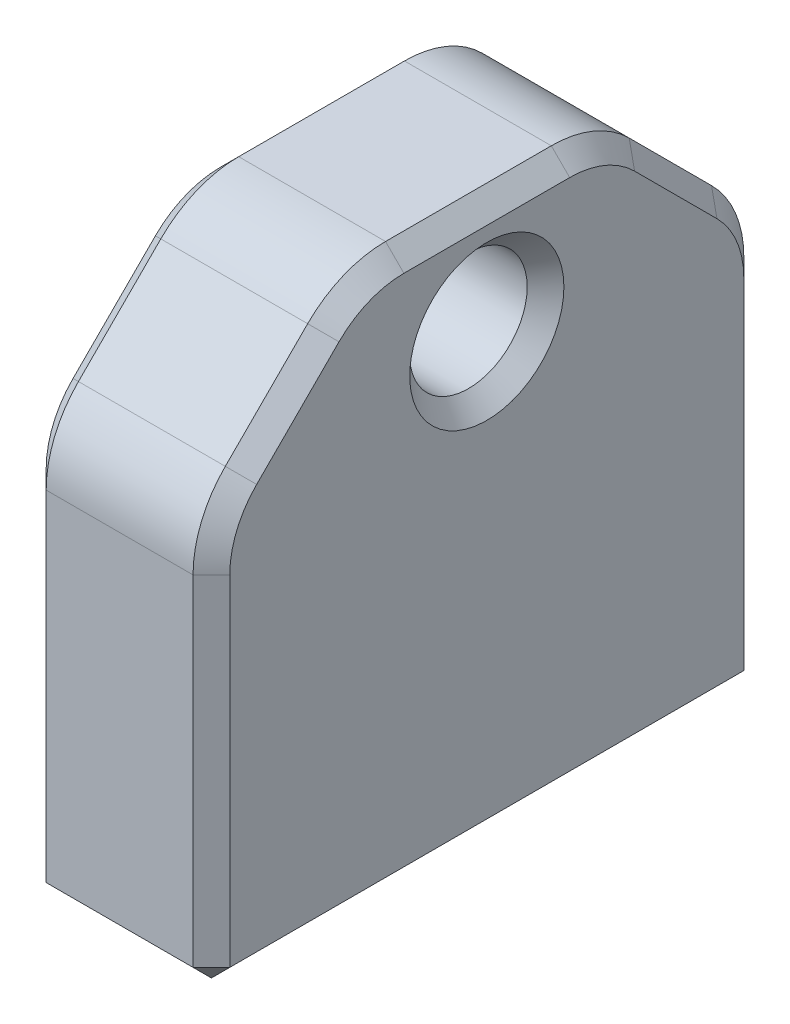
SolidWorks part; units mm, degrees
ref_plane "Front Plane" through (0, 0, 0) normal (0, 0, 1) x (1, 0, 0)
ref_plane "Top Plane" through (0, 0, 0) normal (0, 1, 0) x (1, 0, 0)
ref_plane "Right Plane" through (0, 0, 0) normal (1, 0, 0) x (0, 0, -1)
sketch "Sketch1" plane through (0, 0, 0) normal (0, 1, 0) x (1, 0, 0)
  line L0 (0, 6.35) -> (0, -6.35) construction
  line L1 (-3.175, 9.525) -> (3.175, 9.525)
  line L2 (-3.175, 9.525) -> (-3.175, -9.525)
  line L3 (-3.175, -9.525) -> (3.175, -9.525)
  line L4 (3.175, 9.525) -> (3.175, -9.525)
  line L5 (-3.175, 9.525) -> (3.175, -9.525) construction
  line L6 (-3.175, -9.525) -> (3.175, 9.525) construction
  circle A0 centre (0, 6.35) radius 2.032
  circle A1 centre (0, -6.35) radius 2.032
  point P0 (0, 0)
  point P9 (0, 0)
  dimension "D3" = 4.064
  dimension "D1" = 19.05
  dimension "D2" = 6.35
  dimension "D4" = 12.7
extrude "Boss-Extrude1" add sketch "Sketch1" along normal blind 19.05 contours L2 L3 L4 L1
sketch "Sketch2" plane through (-3.175, 0, 0) normal (-1, 0, 0) x (0, 0, 1)
  line L0 (0, 19.05) -> (0, 15.24)
  line L1 (-9.525, 19.05) -> (9.525, 19.05) construction
  circle A0 centre (0, 15.24) radius 2.032
  dimension "D1" = 4.064
  dimension "D2" = 3.81
extrude "Cut-Extrude1" cut sketch "Sketch2" against normal through all contours A0
extrude "Cut-Extrude2" cut sketch "Sketch1<3>" along normal blind 7.62 contours A0 | A1
sketch "Sketch1<3>" plane through (0, 0, 0) normal (0, 1, 0) x (1, 0, 0) same geometry as "Sketch1"
chamfer "Chamfer1" distance 5.08 angle 45 2 edges at (0, 19.05, 9.525) (0, 19.05, -9.525)
fillet "Fillet1" radius 3.81 4 edges at (0, 13.97, 9.525) (0, 19.05, 4.445) (0, 13.97, -9.525) (0, 19.05, -4.445)
chamfer "Chamfer2" distance 0.635 angle 45 26 edges at (3.175, 15.24, 2.032) (0, 0, 9.525) (3.175, 18.76, 4.3249) (3.175, 19.05, 0) (3.175, 18.76, -4.3249) (3.175, 16.51, -6.985) (3.175, 13.8499, -9.235) (3.175, 6.1959, -9.525) (3.175, 16.51, 6.985) (3.175, 13.8499, 9.235) (3.175, 6.1959, 9.525) (3.175, 0, 0) (0, 0, -9.525) (-3.175, 0, 0) (-3.175, 6.1959, -9.525) (-3.175, 13.8499, -9.235) (-3.175, 16.51, -6.985) (-3.175, 18.76, -4.3249) (-3.175, 19.05, 0) (-3.175, 18.76, 4.3249) (-3.175, 16.51, 6.985) (-3.175, 13.8499, 9.235) (-3.175, 6.1959, 9.525) (-3.175, 15.24, 2.032) (0, 0, 8.382) (0, 0, -4.318)
